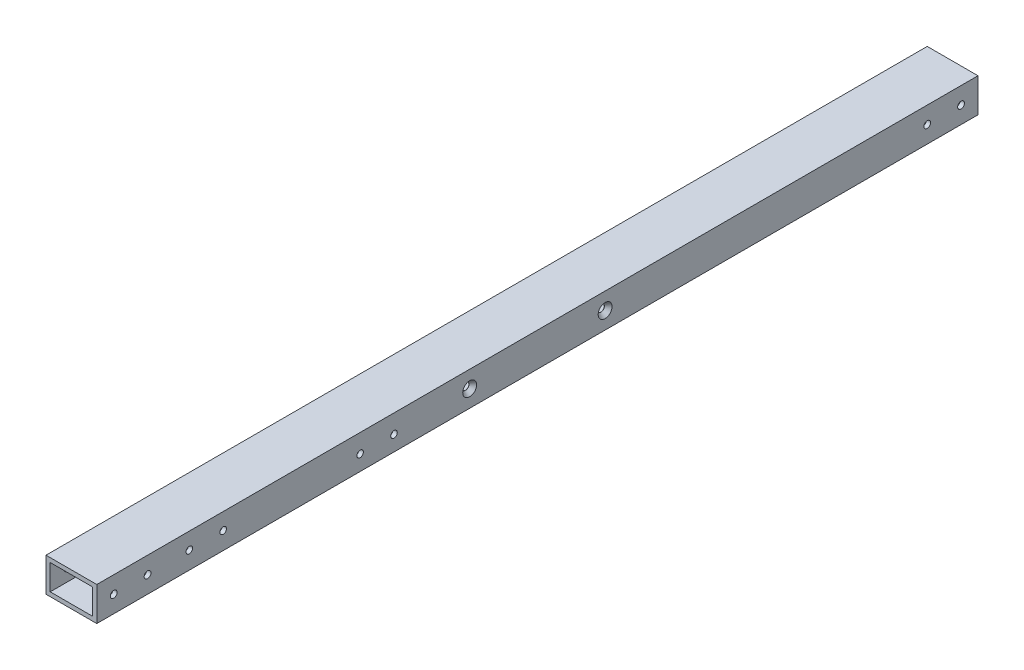
SolidWorks part; units mm, degrees
ref_plane "Front Plane" through (0, 0, 0) normal (0, 0, 1) x (1, 0, 0)
ref_plane "Top Plane" through (0, 0, 0) normal (0, 1, 0) x (1, 0, 0)
ref_plane "Right Plane" through (0, 0, 0) normal (1, 0, 0) x (0, 0, -1)
sketch "Sketch1" plane through (0, 0, 0) normal (0, 0, 1) x (1, 0, 0)
  line L0 (-15.875, 9.525) -> (15.875, 9.525)
  line L2 (-19.05, 12.7) -> (19.05, 12.7)
  line L3 (-19.05, 12.7) -> (-19.05, -12.7)
  line L4 (-19.05, -12.7) -> (19.05, -12.7)
  line L5 (19.05, 12.7) -> (19.05, -12.7)
  line L10 (15.875, 9.525) -> (15.875, -9.525)
  line L11 (-15.875, -9.525) -> (15.875, -9.525)
  line L12 (-15.875, 9.525) -> (-15.875, -9.525)
  point P12 (0, 12.7)
  point P14 (19.05, 0)
  dimension "Wall Thickness" = 3.175
  dimension "Outside Width" = 38.1
  dimension "Outside Height" = 25.4
  dimension "Inside Height" = 19.05
  dimension "Inside Width" = 31.75
sketch "Sketch2" plane through (0, 0, 0) normal (1, 0, 0) x (0, 0, -1)
  line L0 (330.5556, 0) -> (-330.5556, 0)
  point P4 (0, 0)
  point P7 (-330.5556, 0)
  point P10 (330.5556, 0)
  dimension "Length" = 661.1112
sketch "Sketch3" plane through (0, 0, 0) normal (0, 0, 1) x (1, 0, 0)
  line L21 (19.05, 12.7) -> (-19.05, 12.7)
  line L22 (19.05, -12.7) -> (19.05, 12.7)
  line L23 (-19.05, -12.7) -> (19.05, -12.7)
  line L24 (-19.05, 12.7) -> (-19.05, -12.7)
  line L25 (19.05, 12.7) -> (-19.05, 12.7)
  line L26 (19.05, -12.7) -> (19.05, 12.7)
  line L27 (-19.05, -12.7) -> (19.05, -12.7)
  line L28 (-19.05, 12.7) -> (-19.05, -12.7)
  line L29 (15.875, 9.525) -> (-15.875, 9.525)
  line L30 (15.875, -9.525) -> (15.875, 9.525)
  line L31 (-15.875, -9.525) -> (15.875, -9.525)
  line L32 (-15.875, 9.525) -> (-15.875, -9.525)
  line L33 (15.875, 9.525) -> (-15.875, 9.525)
  line L34 (15.875, -9.525) -> (15.875, 9.525)
  line L35 (-15.875, -9.525) -> (15.875, -9.525)
  line L36 (-15.875, 9.525) -> (-15.875, -9.525)
  dimension "D1" = 0
  dimension "D2" = 0
extrude "Boss-Extrude1" add sketch "Sketch3" along normal up to vertex (330.5556 mm away) and the other way up to vertex (330.5556 mm away) up to point (0, 0, 330.5556) other way up to point (0, 0, -330.5556)
sketch "Drawing Reference" plane through (0, 0, 0) normal (1, 0, 0) x (0, 0, -1)
  line L0 (-330.5556, 0) -> (330.5556, 0) construction
  line L1 (0, -12.7) -> (0, 12.7) construction
  line L2 (-330.5556, -12.7) -> (330.5556, -12.7) construction
  line L5 (-330.5556, 12.7) -> (330.5556, 12.7) construction
  point P7 (-303.1236, 0)
  point P8 (303.1236, 0)
  dimension "D1" = 27.432
sketch "Sketch4" plane through (-19.05, 0, 0) normal (-1, 0, 0) x (0, 0, 1)
  line L0 (-330.5556, 0) -> (-317.8556, 0)
  line L1 (-330.5556, 12.7) -> (-330.5556, -12.7) construction
  line L2 (-317.8556, 0) -> (-292.4556, 0)
  line L3 (330.5556, 12.7) -> (330.5556, -12.7) construction
  line L4 (330.5556, 0) -> (317.8556, 0)
  line L5 (317.8556, 0) -> (292.4556, 0)
  line L6 (0, 0) -> (50.8, 0) construction
  line L7 (0, 0) -> (-50.8, 0) construction
  point P11 (-317.8556, 0)
  point P13 (-292.4556, 0)
  point P14 (317.8556, 0)
  point P15 (292.4556, 0)
hole_wizard "#10 Clearance Hole2" positions "Sketch11" profile "Sketch12" hole size "#10" standard "ANSI Inch" end condition through all
sketch "Sketch11" plane through (-19.05, 0, 0) normal (-1, 0, 0) x (0, 0, 1)
  point P0 (-317.8556, 0)
  point P3 (-292.4556, 0)
  point P6 (292.4556, 0)
  point P9 (317.8556, 0)
sketch "Sketch12" plane through (-19.05, 0, -317.8556) normal (0, 1, 0) x (0, 0, 1)
  line L0 (0, 0) -> (0, 38.1)
  line L1 (0, 38.1) -> (2.5527, 38.1)
  line L2 (2.5527, 38.1) -> (2.5527, 0)
  line L5 (2.5527, 0) -> (0, 0)
  line L11 (0, -6.35) -> (0, 107.95) construction
  dimension "Thru Hole Dia." = 5.1054
  dimension "Thru Hole Depth" = 38.1
hole_wizard "#10 (0.1935) Diameter Hole1" positions "Sketch14" profile "Sketch16" hole size "#10" standard "ANSI Inch" end condition through all
sketch "Sketch14" plane through (19.05, 0, 0) normal (1, 0, 0) x (0, 0, -1)
  point P10 (-132.9849, -1.2316)
  point P13 (-107.5849, -1.2316)
  point P17 (-261.1289, 0.3559)
  point P20 (-235.7289, 0.3559)
sketch "Sketch16" plane through (19.05, -1.2316, 132.9849) normal (0, 1, 0) x (0, 0, -1)
  line L0 (0, 0) -> (0, 38.1)
  line L1 (0, 38.1) -> (2.4574, 38.1)
  line L2 (2.4574, 38.1) -> (2.4574, 0)
  line L5 (2.4574, 0) -> (0, 0)
  line L11 (0, -6.35) -> (0, 107.95) construction
  dimension "Thru Hole Dia." = 4.9149
  dimension "Thru Hole Depth" = 38.1
sketch "Sketch17" plane through (19.05, 0, 0) normal (1, 0, 0) x (0, 0, -1)
  point P0 (-261.1289, 0.3559)
  point P1 (-235.7289, 0.3559)
hole_wizard "#10 (0.1935) Diameter Hole2" positions "Sketch18" profile "Sketch19" hole size "#10" standard "ANSI Inch" end condition through all
sketch "Sketch18" plane through (19.05, 0, 0) normal (1, 0, 0) x (0, 0, -1)
  point P0 (-261.1289, 0.3559)
  point P3 (-235.7289, 0.3559)
sketch "Sketch19" plane through (19.05, 0.3559, 261.1289) normal (0, 1, 0) x (0, 0, -1)
  line L0 (0, 0) -> (0, 38.1)
  line L1 (0, 38.1) -> (2.4574, 38.1)
  line L2 (2.4574, 38.1) -> (2.4574, 0)
  line L5 (2.4574, 0) -> (0, 0)
  line L11 (0, -6.35) -> (0, 107.95) construction
  dimension "Thru Hole Dia." = 4.9149
  dimension "Thru Hole Depth" = 38.1
hole_wizard "#10 Clearance Hole3" positions "Sketch20" profile "Sketch21" hole size "#10" standard "ANSI Inch" end condition through all
sketch "Sketch20" plane through (-19.05, 0, 0) normal (-1, 0, 0) x (0, 0, 1)
  point P0 (-50.8, 0)
  point P3 (50.8, 0)
sketch "Sketch21" plane through (-19.05, 0, -50.8) normal (0, 1, 0) x (0, 0, 1)
  line L0 (0, 0) -> (0, 38.1)
  line L1 (0, 38.1) -> (5.207, 38.1)
  line L2 (2.5527, 35.0466) -> (2.5527, 0)
  line L5 (2.5527, 0) -> (0, 0)
  line L7 (5.207, 38.1) -> (2.5527, 35.0466)
  line L8 (-5.207, 38.1) -> (-2.5527, 35.0466) construction
  line L11 (0, -6.35) -> (0, 107.95) construction
  dimension "Thru Hole Dia." = 5.1054
  dimension "Thru Hole Depth" = 38.1
  dimension "Far C'Sink Dia." = 10.414
  dimension "Far C'Sink Angle" = 82
equation "\"D1@Drawing Reference\"=\"Outside Width@Sketch1\" * 0.72"
